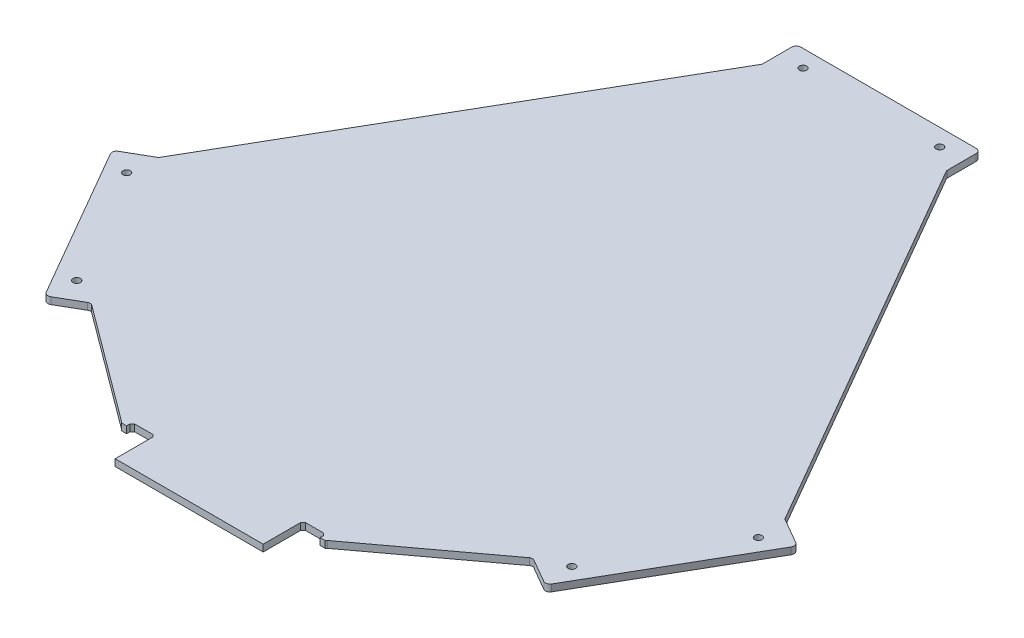
SolidWorks part; units mm, degrees
ref_plane "正面" through (0, 0, 0) normal (0, 0, 1) x (1, 0, 0)
ref_plane "平面" through (0, 0, 0) normal (0, 1, 0) x (1, 0, 0)
ref_plane "右側面" through (0, 0, 0) normal (1, 0, 0) x (0, 0, -1)
sketch "ｽｹｯﾁ1" plane through (0, 0, 0) normal (0, 1, 0) x (1, 0, 0)
  line L0 (70.5, 135.4) -> (70.5, 150.4) construction
  line L1 (70.5, 150.4) -> (-70.5, 150.4) construction
  line L2 (-70.5, 150.4) -> (-70.5, 135.4) construction
  line L3 (-70.5, 135.4) -> (70.5, 135.4) construction
  line L4 (70.1305, 165.2152) -> (41.4674, 150.8837) construction
  line L5 (40.5, 149.3184) -> (40.5, 136.5492) construction
  line L6 (41.5546, 134.9433) -> (99.6921, 109.7691) construction
  line L7 (101.2625, 109.8594) -> (111.9748, 116.0442) construction
  line L8 (112.6154, 118.4348) -> (86.0052, 164.525) construction
  line L9 (84.4896, 165.4) -> (70.9131, 165.4) construction
  line L10 (98.4904, 142.9) -> (85.5, 135.4) construction
  line L11 (85.5, 135.4) -> (160.01, 6.3449) construction
  line L12 (160.01, 6.3449) -> (173.0004, 13.8449) construction
  line L13 (173.0004, 13.8449) -> (98.4904, 142.9) construction
  line L14 (138.5051, -33.2006) -> (149.5636, -39.5852) construction
  line L15 (151.4028, -39.53) -> (178.1458, -21.8728) construction
  line L16 (178.6972, -21.2874) -> (185.4854, -9.5298) construction
  line L17 (185.4854, -7.7798) -> (158.8752, 38.3104) construction
  line L18 (156.4847, 38.9509) -> (145.7723, 32.7661) construction
  line L19 (144.9088, 31.4513) -> (137.6417, -31.4843) construction
  line L20 (82.0098, -128.7548) -> (95.0002, -136.2548) construction
  line L21 (95.0002, -136.2548) -> (165.5002, -14.1452) construction
  line L22 (165.5002, -14.1452) -> (152.5098, -6.6452) construction
  line L23 (152.5098, -6.6452) -> (82.0098, -128.7548) construction
  line L24 (108.0154, -143.3424) -> (109.9354, -111.3536) construction
  line L25 (109.0636, -109.7332) -> (98.0051, -103.3487) construction
  line L26 (96.087, -103.459) -> (45.2168, -141.2204) construction
  line L27 (44.5098, -142.6256) -> (44.5098, -154.9952) construction
  line L28 (46.2598, -156.7452) -> (99.4802, -156.7452) construction
  line L29 (100.9958, -155.8702) -> (107.784, -144.1126) construction
  line L30 (-98.0051, -103.3487) -> (-109.0636, -109.7332) construction
  line L31 (-109.9354, -111.3536) -> (-108.0154, -143.3424) construction
  line L32 (-107.784, -144.1126) -> (-100.9958, -155.8702) construction
  line L33 (-99.4802, -156.7452) -> (-46.2598, -156.7452) construction
  line L34 (-44.5098, -154.9952) -> (-44.5098, -142.6256) construction
  line L35 (-45.2168, -141.2204) -> (-96.087, -103.459) construction
  line L36 (-152.5098, -6.6452) -> (-165.5002, -14.1452) construction
  line L37 (-165.5002, -14.1452) -> (-95.0002, -136.2548) construction
  line L38 (-95.0002, -136.2548) -> (-82.0098, -128.7548) construction
  line L39 (-82.0098, -128.7548) -> (-152.5098, -6.6452) construction
  line L40 (-178.1458, -21.8728) -> (-151.4028, -39.53) construction
  line L41 (-149.5636, -39.5852) -> (-138.5051, -33.2006) construction
  line L42 (-137.6417, -31.4843) -> (-144.9088, 31.4513) construction
  line L43 (-145.7723, 32.7661) -> (-156.4847, 38.9509) construction
  line L44 (-158.8752, 38.3104) -> (-185.4854, -7.7798) construction
  line L45 (-185.4854, -9.5298) -> (-178.6972, -21.2874) construction
  line L46 (-40.5, 136.5492) -> (-40.5, 149.3184) construction
  line L47 (-41.4674, 150.8837) -> (-70.1305, 165.2152) construction
  line L48 (-70.9131, 165.4) -> (-84.4896, 165.4) construction
  line L49 (-86.0052, 164.525) -> (-112.6154, 118.4348) construction
  line L50 (-111.9748, 116.0442) -> (-101.2625, 109.8594) construction
  line L51 (-99.6921, 109.7691) -> (-41.5546, 134.9433) construction
  line L52 (-85.5, 135.4) -> (-98.4904, 142.9) construction
  line L53 (-98.4904, 142.9) -> (-173.0004, 13.8449) construction
  line L54 (-173.0004, 13.8449) -> (-160.01, 6.3449) construction
  line L55 (-160.01, 6.3449) -> (-85.5, 135.4) construction
  line L56 (70.5, 135.4) -> (70.5, 150.4)
  line L57 (70.5, 150.4) -> (-70.5, 150.4)
  line L58 (-70.5, 150.4) -> (-70.5, 135.4)
  line L59 (-70.5, 135.4) -> (70.5, 135.4)
  line L60 (70.1305, 165.2152) -> (41.4674, 150.8837)
  line L61 (40.5, 149.3184) -> (40.5, 136.5492)
  line L62 (41.5546, 134.9433) -> (99.6921, 109.7691)
  line L63 (101.2625, 109.8594) -> (111.9748, 116.0442)
  line L64 (112.6154, 118.4348) -> (86.0052, 164.525)
  line L65 (84.4896, 165.4) -> (70.9131, 165.4)
  line L66 (98.4904, 142.9) -> (85.5, 135.4)
  line L67 (85.5, 135.4) -> (160.01, 6.3449)
  line L68 (160.01, 6.3449) -> (173.0004, 13.8449)
  line L69 (173.0004, 13.8449) -> (98.4904, 142.9)
  line L70 (138.5051, -33.2006) -> (149.5636, -39.5852)
  line L71 (151.4028, -39.53) -> (178.1458, -21.8728)
  line L72 (178.6972, -21.2874) -> (185.4854, -9.5298)
  line L73 (185.4854, -7.7798) -> (158.8752, 38.3104)
  line L74 (156.4847, 38.9509) -> (145.7723, 32.7661)
  line L75 (144.9088, 31.4513) -> (137.6417, -31.4843)
  line L76 (82.0098, -128.7548) -> (95.0002, -136.2548)
  line L77 (95.0002, -136.2548) -> (165.5002, -14.1452)
  line L78 (165.5002, -14.1452) -> (152.5098, -6.6452)
  line L79 (152.5098, -6.6452) -> (82.0098, -128.7548)
  line L80 (108.0154, -143.3424) -> (109.9354, -111.3536)
  line L81 (109.0636, -109.7332) -> (98.0051, -103.3487)
  line L82 (96.087, -103.459) -> (45.2168, -141.2204)
  line L83 (44.5098, -142.6256) -> (44.5098, -154.9952)
  line L84 (46.2598, -156.7452) -> (99.4802, -156.7452)
  line L85 (100.9958, -155.8702) -> (107.784, -144.1126)
  line L86 (-98.0051, -103.3487) -> (-109.0636, -109.7332)
  line L87 (-109.9354, -111.3536) -> (-108.0154, -143.3424)
  line L88 (-107.784, -144.1126) -> (-100.9958, -155.8702)
  line L89 (-99.4802, -156.7452) -> (-46.2598, -156.7452)
  line L90 (-44.5098, -154.9952) -> (-44.5098, -142.6256)
  line L91 (-45.2168, -141.2204) -> (-96.087, -103.459)
  line L92 (-152.5098, -6.6452) -> (-165.5002, -14.1452)
  line L93 (-165.5002, -14.1452) -> (-95.0002, -136.2548)
  line L94 (-95.0002, -136.2548) -> (-82.0098, -128.7548)
  line L95 (-82.0098, -128.7548) -> (-152.5098, -6.6452)
  line L96 (-178.1458, -21.8728) -> (-151.4028, -39.53)
  line L97 (-149.5636, -39.5852) -> (-138.5051, -33.2006)
  line L98 (-137.6417, -31.4843) -> (-144.9088, 31.4513)
  line L99 (-145.7723, 32.7661) -> (-156.4847, 38.9509)
  line L100 (-158.8752, 38.3104) -> (-185.4854, -7.7798)
  line L101 (-185.4854, -9.5298) -> (-178.6972, -21.2874)
  line L102 (-40.5, 136.5492) -> (-40.5, 149.3184)
  line L103 (-41.4674, 150.8837) -> (-70.1305, 165.2152)
  line L104 (-70.9131, 165.4) -> (-84.4896, 165.4)
  line L105 (-86.0052, 164.525) -> (-112.6154, 118.4348)
  line L106 (-111.9748, 116.0442) -> (-101.2625, 109.8594)
  line L107 (-99.6921, 109.7691) -> (-41.5546, 134.9433)
  line L108 (-85.5, 135.4) -> (-98.4904, 142.9)
  line L109 (-98.4904, 142.9) -> (-173.0004, 13.8449)
  line L110 (-173.0004, 13.8449) -> (-160.01, 6.3449)
  line L111 (-160.01, 6.3449) -> (-85.5, 135.4)
  line L112 (82.0098, -128.7548) -> (95.0002, -136.2548)
  line L113 (95.0002, -136.2548) -> (165.5002, -14.1452)
  line L114 (165.5002, -14.1452) -> (152.5098, -6.6452)
  line L115 (152.5098, -6.6452) -> (82.0098, -128.7548)
  line L116 (-152.5098, -6.6452) -> (-165.5002, -14.1452)
  line L117 (-165.5002, -14.1452) -> (-95.0002, -136.2548)
  line L118 (-95.0002, -136.2548) -> (-82.0098, -128.7548)
  line L119 (-82.0098, -128.7548) -> (-152.5098, -6.6452)
  line L120 (70.5, 135.4) -> (70.5, 150.4)
  line L121 (70.5, 150.4) -> (-70.5, 150.4)
  line L122 (-70.5, 150.4) -> (-70.5, 135.4)
  line L123 (-70.5, 135.4) -> (70.5, 135.4)
  line L124 (-40.5, 136.5492) -> (-40.5, 135.4)
  line L125 (-40.5, 135.4) -> (-137.5098, -32.626)
  line L126 (-137.5098, -32.626) -> (-138.5051, -33.2006)
  line L127 (-98.0051, -103.3487) -> (-97.0098, -102.774)
  line L128 (-97.0098, -102.774) -> (97.0098, -102.774)
  line L129 (97.0098, -102.774) -> (98.0051, -103.3487)
  line L130 (138.5051, -33.2006) -> (137.5098, -32.626)
  line L131 (137.5098, -32.626) -> (40.5, 135.4)
  line L132 (40.5, 135.4) -> (40.5, 136.5492)
  line L133 (-40.5, 149.3184) -> (-40.5, 150.4)
  line L134 (40.5, 149.3184) -> (40.5, 150.4)
  line L135 (149.5636, -39.5852) -> (150.5002, -40.126)
  line L136 (109.0636, -109.7332) -> (110.0002, -110.274)
  line L137 (-109.0636, -109.7332) -> (-110.0002, -110.274)
  line L138 (-149.5636, -39.5852) -> (-150.5002, -40.126)
  arc A0 (41.4674, 150.8837) -> (40.5, 149.3184) centre (42.25, 149.3184) ccw construction
  arc A1 (40.5, 136.5492) -> (41.5546, 134.9433) centre (42.25, 136.5492) ccw construction
  arc A2 (99.6921, 109.7691) -> (101.2625, 109.8594) centre (100.3875, 111.375) ccw construction
  arc A3 (111.9748, 116.0442) -> (112.6154, 118.4348) centre (111.0998, 117.5598) ccw construction
  arc A4 (86.0052, 164.525) -> (84.4896, 165.4) centre (84.4896, 163.65) ccw construction
  arc A5 (70.9131, 165.4) -> (70.1305, 165.2152) centre (70.9131, 163.65) ccw construction
  arc A6 (149.5636, -39.5852) -> (151.4028, -39.53) centre (150.4386, -38.0696) ccw construction
  arc A7 (178.1458, -21.8728) -> (178.6972, -21.2874) centre (177.1816, -20.4124) ccw construction
  arc A8 (185.4854, -9.5298) -> (185.4854, -7.7798) centre (183.9699, -8.6548) ccw construction
  arc A9 (158.8752, 38.3104) -> (156.4847, 38.9509) centre (157.3597, 37.4354) ccw construction
  arc A10 (145.7723, 32.7661) -> (144.9088, 31.4513) centre (146.6473, 31.2506) ccw construction
  arc A11 (137.6417, -31.4843) -> (138.5051, -33.2006) centre (139.3801, -31.685) ccw construction
  arc A12 (109.9354, -111.3536) -> (109.0636, -109.7332) centre (108.1886, -111.2488) ccw construction
  arc A13 (98.0051, -103.3487) -> (96.087, -103.459) centre (97.1301, -104.8642) ccw construction
  arc A14 (45.2168, -141.2204) -> (44.5098, -142.6256) centre (46.2598, -142.6256) ccw construction
  arc A15 (44.5098, -154.9952) -> (46.2598, -156.7452) centre (46.2598, -154.9952) ccw construction
  arc A16 (99.4802, -156.7452) -> (100.9958, -155.8702) centre (99.4802, -154.9952) ccw construction
  arc A17 (107.784, -144.1126) -> (108.0154, -143.3424) centre (106.2685, -143.2376) ccw construction
  arc A18 (-109.0636, -109.7332) -> (-109.9354, -111.3536) centre (-108.1886, -111.2488) ccw construction
  arc A19 (-108.0154, -143.3424) -> (-107.784, -144.1126) centre (-106.2685, -143.2376) ccw construction
  arc A20 (-100.9958, -155.8702) -> (-99.4802, -156.7452) centre (-99.4802, -154.9952) ccw construction
  arc A21 (-46.2598, -156.7452) -> (-44.5098, -154.9952) centre (-46.2598, -154.9952) ccw construction
  arc A22 (-44.5098, -142.6256) -> (-45.2168, -141.2204) centre (-46.2598, -142.6256) ccw construction
  arc A23 (-96.087, -103.459) -> (-98.0051, -103.3487) centre (-97.1301, -104.8642) ccw construction
  arc A24 (-151.4028, -39.53) -> (-149.5636, -39.5852) centre (-150.4386, -38.0696) ccw construction
  arc A25 (-138.5051, -33.2006) -> (-137.6417, -31.4843) centre (-139.3801, -31.685) ccw construction
  arc A26 (-144.9088, 31.4513) -> (-145.7723, 32.7661) centre (-146.6473, 31.2506) ccw construction
  arc A27 (-156.4847, 38.9509) -> (-158.8752, 38.3104) centre (-157.3597, 37.4354) ccw construction
  arc A28 (-185.4854, -7.7798) -> (-185.4854, -9.5298) centre (-183.9699, -8.6548) ccw construction
  arc A29 (-178.6972, -21.2874) -> (-178.1458, -21.8728) centre (-177.1816, -20.4124) ccw construction
  arc A30 (-40.5, 149.3184) -> (-41.4674, 150.8837) centre (-42.25, 149.3184) ccw construction
  arc A31 (-70.1305, 165.2152) -> (-70.9131, 165.4) centre (-70.9131, 163.65) ccw construction
  arc A32 (-84.4896, 165.4) -> (-86.0052, 164.525) centre (-84.4896, 163.65) ccw construction
  arc A33 (-112.6154, 118.4348) -> (-111.9748, 116.0442) centre (-111.0998, 117.5598) ccw construction
  arc A34 (-101.2625, 109.8594) -> (-99.6921, 109.7691) centre (-100.3875, 111.375) ccw construction
  arc A35 (-41.5546, 134.9433) -> (-40.5, 136.5492) centre (-42.25, 136.5492) ccw construction
  arc A36 (41.4674, 150.8837) -> (40.5, 149.3184) centre (42.25, 149.3184) ccw
  arc A37 (40.5, 136.5492) -> (41.5546, 134.9433) centre (42.25, 136.5492) ccw
  arc A38 (99.6921, 109.7691) -> (101.2625, 109.8594) centre (100.3875, 111.375) ccw
  arc A39 (111.9748, 116.0442) -> (112.6154, 118.4348) centre (111.0998, 117.5598) ccw
  arc A40 (86.0052, 164.525) -> (84.4896, 165.4) centre (84.4896, 163.65) ccw
  arc A41 (70.9131, 165.4) -> (70.1305, 165.2152) centre (70.9131, 163.65) ccw
  arc A42 (149.5636, -39.5852) -> (151.4028, -39.53) centre (150.4386, -38.0696) ccw
  arc A43 (178.1458, -21.8728) -> (178.6972, -21.2874) centre (177.1816, -20.4124) ccw
  arc A44 (185.4854, -9.5298) -> (185.4854, -7.7798) centre (183.9699, -8.6548) ccw
  arc A45 (158.8752, 38.3104) -> (156.4847, 38.9509) centre (157.3597, 37.4354) ccw
  arc A46 (145.7723, 32.7661) -> (144.9088, 31.4513) centre (146.6473, 31.2506) ccw
  arc A47 (137.6417, -31.4843) -> (138.5051, -33.2006) centre (139.3801, -31.685) ccw
  arc A48 (109.9354, -111.3536) -> (109.0636, -109.7332) centre (108.1886, -111.2488) ccw
  arc A49 (98.0051, -103.3487) -> (96.087, -103.459) centre (97.1301, -104.8642) ccw
  arc A50 (45.2168, -141.2204) -> (44.5098, -142.6256) centre (46.2598, -142.6256) ccw
  arc A51 (44.5098, -154.9952) -> (46.2598, -156.7452) centre (46.2598, -154.9952) ccw
  arc A52 (99.4802, -156.7452) -> (100.9958, -155.8702) centre (99.4802, -154.9952) ccw
  arc A53 (107.784, -144.1126) -> (108.0154, -143.3424) centre (106.2685, -143.2376) ccw
  arc A54 (-109.0636, -109.7332) -> (-109.9354, -111.3536) centre (-108.1886, -111.2488) ccw
  arc A55 (-108.0154, -143.3424) -> (-107.784, -144.1126) centre (-106.2685, -143.2376) ccw
  arc A56 (-100.9958, -155.8702) -> (-99.4802, -156.7452) centre (-99.4802, -154.9952) ccw
  arc A57 (-46.2598, -156.7452) -> (-44.5098, -154.9952) centre (-46.2598, -154.9952) ccw
  arc A58 (-44.5098, -142.6256) -> (-45.2168, -141.2204) centre (-46.2598, -142.6256) ccw
  arc A59 (-96.087, -103.459) -> (-98.0051, -103.3487) centre (-97.1301, -104.8642) ccw
  arc A60 (-151.4028, -39.53) -> (-149.5636, -39.5852) centre (-150.4386, -38.0696) ccw
  arc A61 (-138.5051, -33.2006) -> (-137.6417, -31.4843) centre (-139.3801, -31.685) ccw
  arc A62 (-144.9088, 31.4513) -> (-145.7723, 32.7661) centre (-146.6473, 31.2506) ccw
  arc A63 (-156.4847, 38.9509) -> (-158.8752, 38.3104) centre (-157.3597, 37.4354) ccw
  arc A64 (-185.4854, -7.7798) -> (-185.4854, -9.5298) centre (-183.9699, -8.6548) ccw
  arc A65 (-178.6972, -21.2874) -> (-178.1458, -21.8728) centre (-177.1816, -20.4124) ccw
  arc A66 (-40.5, 149.3184) -> (-41.4674, 150.8837) centre (-42.25, 149.3184) ccw
  arc A67 (-70.1305, 165.2152) -> (-70.9131, 165.4) centre (-70.9131, 163.65) ccw
  arc A68 (-84.4896, 165.4) -> (-86.0052, 164.525) centre (-84.4896, 163.65) ccw
  arc A69 (-112.6154, 118.4348) -> (-111.9748, 116.0442) centre (-111.0998, 117.5598) ccw
  arc A70 (-101.2625, 109.8594) -> (-99.6921, 109.7691) centre (-100.3875, 111.375) ccw
  arc A71 (-41.5546, 134.9433) -> (-40.5, 136.5492) centre (-42.25, 136.5492) ccw
  circle A73 centre (108.755, -97.4308) radius 1.6
  circle A74 centre (108.755, -97.4308) radius 1.6
  circle A75 centre (156.505, -14.7253) radius 1.6
  circle A76 centre (156.505, -14.7253) radius 1.6
  circle A77 centre (146.505, -32.0458) radius 1.6
  circle A78 centre (146.505, -32.0458) radius 1.6
  circle A79 centre (101.005, -110.8542) radius 1.6
  circle A80 centre (101.005, -110.8542) radius 1.6
  circle A81 centre (138.755, -45.4692) radius 1.6
  circle A82 centre (138.755, -45.4692) radius 1.6
  circle A83 centre (91.005, -128.1747) radius 1.6
  circle A84 centre (91.005, -128.1747) radius 1.6
  circle A85 centre (-138.755, -45.4692) radius 1.6
  circle A86 centre (-138.755, -45.4692) radius 1.6
  circle A87 centre (-91.005, -128.1747) radius 1.6
  circle A88 centre (-91.005, -128.1747) radius 1.6
  circle A89 centre (-101.005, -110.8542) radius 1.6
  circle A90 centre (-101.005, -110.8542) radius 1.6
  circle A91 centre (-146.505, -32.0458) radius 1.6
  circle A92 centre (-146.505, -32.0458) radius 1.6
  circle A93 centre (-108.755, -97.4308) radius 1.6
  circle A94 centre (-108.755, -97.4308) radius 1.6
  circle A95 centre (-156.505, -14.7253) radius 1.6
  circle A96 centre (-156.505, -14.7253) radius 1.6
  circle A97 centre (30, 142.9) radius 1.6
  circle A98 centre (30, 142.9) radius 1.6
  circle A99 centre (-65.5, 142.9) radius 1.6
  circle A100 centre (-65.5, 142.9) radius 1.6
  circle A101 centre (-45.5, 142.9) radius 1.6
  circle A102 centre (-45.5, 142.9) radius 1.6
  circle A103 centre (45.5, 142.9) radius 1.6
  circle A104 centre (45.5, 142.9) radius 1.6
  circle A105 centre (-30, 142.9) radius 1.6
  circle A106 centre (-30, 142.9) radius 1.6
  circle A107 centre (65.5, 142.9) radius 1.6
  circle A108 centre (65.5, 142.9) radius 1.6
  dimension "D1" = 0
  dimension "D2" = 0
  dimension "D3" = 0
  dimension "D4" = 0
  dimension "D5" = 0
  dimension "D6" = 0
  dimension "D7" = 0
  dimension "D8" = 0
  dimension "D9" = 0
  dimension "D10" = 0
  dimension "D11" = 0
  dimension "D12" = 0
  dimension "D13" = 0
  dimension "D14" = 0
  dimension "D15" = 0
  dimension "D16" = 0
  dimension "D17" = 0
  dimension "D18" = 0
extrude "ﾎﾞｽ - 押し出し1" add sketch "ｽｹｯﾁ1" along normal mid plane 3 contours L115 L131 L123 L125 L119 L128 | A60 L117 A54 L86 L127 L119 L126 L97 A94 A86 | A48 L113 A42 L70 L130 L115 L128 L129 L81 A82 A74 | A66 L102 L124 L123 L132 L61 A36 L121 A106 A98 region at (0, 0, 0) region at (0, 0, -142.9) region at (123.755, 0, 71.45) region at (-123.755, 0, 71.45)
fillet "ﾌｨﾚｯﾄ1" radius 2 12 edges at (-97.0098, 0, 102.774) (-150.5002, 0, 40.126) (-137.5098, 0, 32.626) (-40.5, 0, -135.4) (-40.5, 0, -150.4) (40.5, 0, -150.4) (40.5, 0, -135.4) (137.5098, 0, 32.626) (150.5002, 0, 40.126) (110.0002, 0, 110.274) (97.0098, 0, 102.774) (-110.0002, 0, 110.274)
sketch "ｽｹｯﾁ4" plane through (0, 0, 0) normal (0, 1, 0) x (1, 0, 0)
  line L0 (108.0154, -143.3424) -> (109.9354, -111.3536) construction
  line L1 (109.0636, -109.7332) -> (98.0051, -103.3487) construction
  line L2 (96.087, -103.459) -> (45.2168, -141.2204) construction
  line L3 (44.5098, -142.6256) -> (44.5098, -154.9952) construction
  line L4 (46.2598, -156.7452) -> (99.4802, -156.7452) construction
  line L5 (100.9958, -155.8702) -> (107.784, -144.1126) construction
  line L6 (-98.0051, -103.3487) -> (-109.0636, -109.7332) construction
  line L7 (-109.9354, -111.3536) -> (-108.0154, -143.3424) construction
  line L8 (-107.784, -144.1126) -> (-100.9958, -155.8702) construction
  line L9 (-99.4802, -156.7452) -> (-46.2598, -156.7452) construction
  line L10 (-44.5098, -154.9952) -> (-44.5098, -142.6256) construction
  line L11 (-45.2168, -141.2204) -> (-96.087, -103.459) construction
  line L12 (108.0154, -143.3424) -> (109.9354, -111.3536)
  line L13 (109.0636, -109.7332) -> (98.0051, -103.3487)
  line L14 (96.087, -103.459) -> (45.2168, -141.2204)
  line L15 (44.5098, -142.6256) -> (44.5098, -154.9952)
  line L16 (46.2598, -156.7452) -> (99.4802, -156.7452)
  line L17 (100.9958, -155.8702) -> (107.784, -144.1126)
  line L18 (-98.0051, -103.3487) -> (-109.0636, -109.7332)
  line L19 (-109.9354, -111.3536) -> (-108.0154, -143.3424)
  line L20 (-107.784, -144.1126) -> (-100.9958, -155.8702)
  line L21 (-99.4802, -156.7452) -> (-46.2598, -156.7452)
  line L22 (-44.5098, -154.9952) -> (-44.5098, -142.6256)
  line L23 (-45.2168, -141.2204) -> (-96.087, -103.459)
  line L24 (32.5002, -141.7452) -> (32.5002, -300.3352) construction
  line L25 (32.5002, -300.3352) -> (42.5002, -300.3352) construction
  line L26 (42.5002, -300.3352) -> (42.5002, -141.7452) construction
  line L27 (42.5002, -141.7452) -> (32.5002, -141.7452) construction
  line L28 (-74.5098, -141.7452) -> (-74.5098, -156.7452)
  line L29 (-74.5098, -156.7452) -> (74.5102, -156.7452)
  line L30 (74.5102, -156.7452) -> (74.5102, -141.7452)
  line L31 (74.5102, -141.7452) -> (-74.5098, -141.7452)
  line L32 (-74.5098, -141.7452) -> (-74.5098, -156.7452)
  line L33 (-74.5098, -156.7452) -> (74.5102, -156.7452)
  line L34 (74.5102, -156.7452) -> (74.5102, -141.7452)
  line L35 (74.5102, -141.7452) -> (-74.5098, -141.7452)
  line L36 (-42.4998, -141.7502) -> (-42.4998, -300.3402) construction
  line L37 (-42.4998, -300.3402) -> (-32.4998, -300.3402) construction
  line L38 (-32.4998, -300.3402) -> (-32.4998, -141.7502) construction
  line L39 (-32.4998, -141.7502) -> (-42.4998, -141.7502) construction
  line L40 (32.5002, -141.7452) -> (42.5002, -141.7452) construction
  line L41 (32.5002, -141.7452) -> (32.5002, -300.3352)
  line L42 (32.5002, -300.3352) -> (42.5002, -300.3352)
  line L43 (42.5002, -300.3352) -> (42.5002, -141.7452)
  line L44 (42.5002, -141.7452) -> (32.5002, -141.7452)
  line L45 (-42.4998, -141.7502) -> (-42.4998, -300.3402)
  line L46 (-42.4998, -300.3402) -> (-32.4998, -300.3402)
  line L47 (-32.4998, -300.3402) -> (-32.4998, -141.7502)
  line L48 (-32.4998, -141.7502) -> (-42.4998, -141.7502)
  line L49 (32.5002, -141.7452) -> (42.5002, -141.7452)
  line L50 (-32.4998, -141.7502) -> (-32.4998, -141.7452)
  line L52 (-32.4998, -140.2502) -> (-42.4998, -140.2502) construction
  line L54 (42.5002, -141.7452) -> (42.5002, -140.2452) construction
  line L55 (32.5002, -140.2452) -> (32.5002, -141.7452) construction
  line L56 (32.5002, -141.7452) -> (42.5002, -141.7452) construction
  line L57 (42.5002, -140.2452) -> (41.5002, -139.2452) construction
  line L58 (41.5002, -139.2452) -> (33.5002, -139.2452) construction
  line L59 (33.5002, -139.2452) -> (32.5002, -140.2452) construction
  line L60 (-32.4998, -141.7502) -> (-32.4998, -140.2502) construction
  line L61 (-42.4998, -140.2502) -> (-42.4998, -141.7502) construction
  line L62 (-137.9739, -32.8939) -> (-148.7682, -39.126)
  line L63 (-149.5002, -41.858) -> (-111.0002, -108.542)
  line L64 (-108.2682, -109.274) -> (-97.4739, -103.042)
  line L65 (-96.4739, -102.774) -> (96.4739, -102.774)
  line L66 (97.4739, -103.042) -> (108.2682, -109.274)
  line L67 (111.0002, -108.542) -> (149.5002, -41.858)
  line L68 (148.7682, -39.126) -> (137.9739, -32.8939)
  line L69 (137.2419, -32.1619) -> (40.7679, 134.9359)
  line L70 (40.5, 135.9359) -> (40.5, 148.4)
  line L71 (38.5, 150.4) -> (-38.5, 150.4)
  line L72 (-40.5, 148.4) -> (-40.5, 135.9359)
  line L73 (-40.7679, 134.9359) -> (-137.2419, -32.1619)
  line L74 (-137.9739, -32.8939) -> (-148.7682, -39.126)
  line L75 (-149.5002, -41.858) -> (-111.0002, -108.542)
  line L76 (-108.2682, -109.274) -> (-97.4739, -103.042)
  line L77 (-96.4739, -102.774) -> (96.4739, -102.774)
  line L78 (97.4739, -103.042) -> (108.2682, -109.274)
  line L79 (111.0002, -108.542) -> (149.5002, -41.858)
  line L80 (148.7682, -39.126) -> (137.9739, -32.8939)
  line L81 (137.2419, -32.1619) -> (40.7679, 134.9359)
  line L82 (40.5, 135.9359) -> (40.5, 148.4)
  line L83 (38.5, 150.4) -> (-38.5, 150.4)
  line L84 (-40.5, 148.4) -> (-40.5, 135.9359)
  line L85 (-40.7679, 134.9359) -> (-137.2419, -32.1619)
  line L86 (-42.4998, -141.7502) -> (-32.4998, -141.7502) construction
  line L87 (-32.4998, -140.2502) -> (-33.4998, -139.2502) construction
  line L88 (-33.4998, -139.2502) -> (-41.4998, -139.2502) construction
  line L89 (-41.4998, -139.2502) -> (-42.4998, -140.2502) construction
  line L90 (42.5002, -141.7452) -> (42.5002, -140.2452)
  line L91 (32.5002, -140.2452) -> (32.5002, -141.7452)
  line L92 (32.5002, -141.7452) -> (42.5002, -141.7452)
  line L93 (42.5002, -140.2452) -> (41.5002, -139.2452)
  line L94 (41.5002, -139.2452) -> (33.5002, -139.2452)
  line L95 (33.5002, -139.2452) -> (32.5002, -140.2452)
  line L96 (-32.4998, -141.7502) -> (-32.4998, -140.2502)
  line L97 (-42.4998, -140.2502) -> (-42.4998, -141.7502)
  line L98 (-42.4998, -141.7502) -> (-32.4998, -141.7502)
  line L99 (-32.4998, -140.2502) -> (-33.4998, -139.2502)
  line L100 (-33.4998, -139.2502) -> (-41.4998, -139.2502)
  line L101 (-41.4998, -139.2502) -> (-42.4998, -140.2502)
  line L102 (-32.4998, -140.2502) -> (-42.4998, -140.2502)
  arc A0 (109.9354, -111.3536) -> (109.0636, -109.7332) centre (108.1886, -111.2488) ccw construction
  arc A1 (98.0051, -103.3487) -> (96.087, -103.459) centre (97.1301, -104.8642) ccw construction
  arc A2 (45.2168, -141.2204) -> (44.5098, -142.6256) centre (46.2598, -142.6256) ccw construction
  arc A3 (44.5098, -154.9952) -> (46.2598, -156.7452) centre (46.2598, -154.9952) ccw construction
  arc A4 (99.4802, -156.7452) -> (100.9958, -155.8702) centre (99.4802, -154.9952) ccw construction
  arc A5 (107.784, -144.1126) -> (108.0154, -143.3424) centre (106.2685, -143.2376) ccw construction
  arc A6 (-109.0636, -109.7332) -> (-109.9354, -111.3536) centre (-108.1886, -111.2488) ccw construction
  arc A7 (-108.0154, -143.3424) -> (-107.784, -144.1126) centre (-106.2685, -143.2376) ccw construction
  arc A8 (-100.9958, -155.8702) -> (-99.4802, -156.7452) centre (-99.4802, -154.9952) ccw construction
  arc A9 (-46.2598, -156.7452) -> (-44.5098, -154.9952) centre (-46.2598, -154.9952) ccw construction
  arc A10 (-44.5098, -142.6256) -> (-45.2168, -141.2204) centre (-46.2598, -142.6256) ccw construction
  arc A11 (-96.087, -103.459) -> (-98.0051, -103.3487) centre (-97.1301, -104.8642) ccw construction
  arc A12 (109.9354, -111.3536) -> (109.0636, -109.7332) centre (108.1886, -111.2488) ccw
  arc A13 (98.0051, -103.3487) -> (96.087, -103.459) centre (97.1301, -104.8642) ccw
  arc A14 (45.2168, -141.2204) -> (44.5098, -142.6256) centre (46.2598, -142.6256) ccw
  arc A15 (44.5098, -154.9952) -> (46.2598, -156.7452) centre (46.2598, -154.9952) ccw
  arc A16 (99.4802, -156.7452) -> (100.9958, -155.8702) centre (99.4802, -154.9952) ccw
  arc A17 (107.784, -144.1126) -> (108.0154, -143.3424) centre (106.2685, -143.2376) ccw
  arc A18 (-109.0636, -109.7332) -> (-109.9354, -111.3536) centre (-108.1886, -111.2488) ccw
  arc A19 (-108.0154, -143.3424) -> (-107.784, -144.1126) centre (-106.2685, -143.2376) ccw
  arc A20 (-100.9958, -155.8702) -> (-99.4802, -156.7452) centre (-99.4802, -154.9952) ccw
  arc A21 (-46.2598, -156.7452) -> (-44.5098, -154.9952) centre (-46.2598, -154.9952) ccw
  arc A22 (-44.5098, -142.6256) -> (-45.2168, -141.2204) centre (-46.2598, -142.6256) ccw
  arc A23 (-96.087, -103.459) -> (-98.0051, -103.3487) centre (-97.1301, -104.8642) ccw
  arc A36 (-148.7682, -39.126) -> (-149.5002, -41.858) centre (-147.7682, -40.858) ccw
  arc A37 (-111.0002, -108.542) -> (-108.2682, -109.274) centre (-109.2682, -107.542) ccw
  arc A38 (-96.4739, -102.774) -> (-97.4739, -103.042) centre (-96.4739, -104.774) ccw
  arc A39 (97.4739, -103.042) -> (96.4739, -102.774) centre (96.4739, -104.774) ccw
  arc A40 (108.2682, -109.274) -> (111.0002, -108.542) centre (109.2682, -107.542) ccw
  arc A41 (149.5002, -41.858) -> (148.7682, -39.126) centre (147.7682, -40.858) ccw
  arc A42 (137.2419, -32.1619) -> (137.9739, -32.8939) centre (138.9739, -31.1619) ccw
  arc A43 (40.5, 135.9359) -> (40.7679, 134.9359) centre (42.5, 135.9359) ccw
  arc A44 (40.5, 148.4) -> (38.5, 150.4) centre (38.5, 148.4) ccw
  arc A45 (-38.5, 150.4) -> (-40.5, 148.4) centre (-38.5, 148.4) ccw
  arc A46 (-40.7679, 134.9359) -> (-40.5, 135.9359) centre (-42.5, 135.9359) ccw
  arc A47 (-137.9739, -32.8939) -> (-137.2419, -32.1619) centre (-138.9739, -31.1619) ccw
  arc A48 (-148.7682, -39.126) -> (-149.5002, -41.858) centre (-147.7682, -40.858) ccw
  arc A49 (-111.0002, -108.542) -> (-108.2682, -109.274) centre (-109.2682, -107.542) ccw
  arc A50 (-96.4739, -102.774) -> (-97.4739, -103.042) centre (-96.4739, -104.774) ccw
  arc A51 (97.4739, -103.042) -> (96.4739, -102.774) centre (96.4739, -104.774) ccw
  arc A52 (108.2682, -109.274) -> (111.0002, -108.542) centre (109.2682, -107.542) ccw
  arc A53 (149.5002, -41.858) -> (148.7682, -39.126) centre (147.7682, -40.858) ccw
  arc A54 (137.2419, -32.1619) -> (137.9739, -32.8939) centre (138.9739, -31.1619) ccw
  arc A55 (40.5, 135.9359) -> (40.7679, 134.9359) centre (42.5, 135.9359) ccw
  arc A56 (40.5, 148.4) -> (38.5, 150.4) centre (38.5, 148.4) ccw
  arc A57 (-38.5, 150.4) -> (-40.5, 148.4) centre (-38.5, 148.4) ccw
  arc A58 (-40.7679, 134.9359) -> (-40.5, 135.9359) centre (-42.5, 135.9359) ccw
  arc A59 (-137.9739, -32.8939) -> (-137.2419, -32.1619) centre (-138.9739, -31.1619) ccw
  dimension "D1" = 0
  dimension "D2" = 0
extrude "ﾎﾞｽ - 押し出し2" add sketch "ｽｹｯﾁ4" along normal mid plane 3 contours L78 A51 L77 A50 L76 A23 L23 A22 L35 A14 L14 A13 | L50 L47 L33 L41 L35 region at (-0.0003, 0, 119.6678) region at (0.0002, 0, 149.2452)
